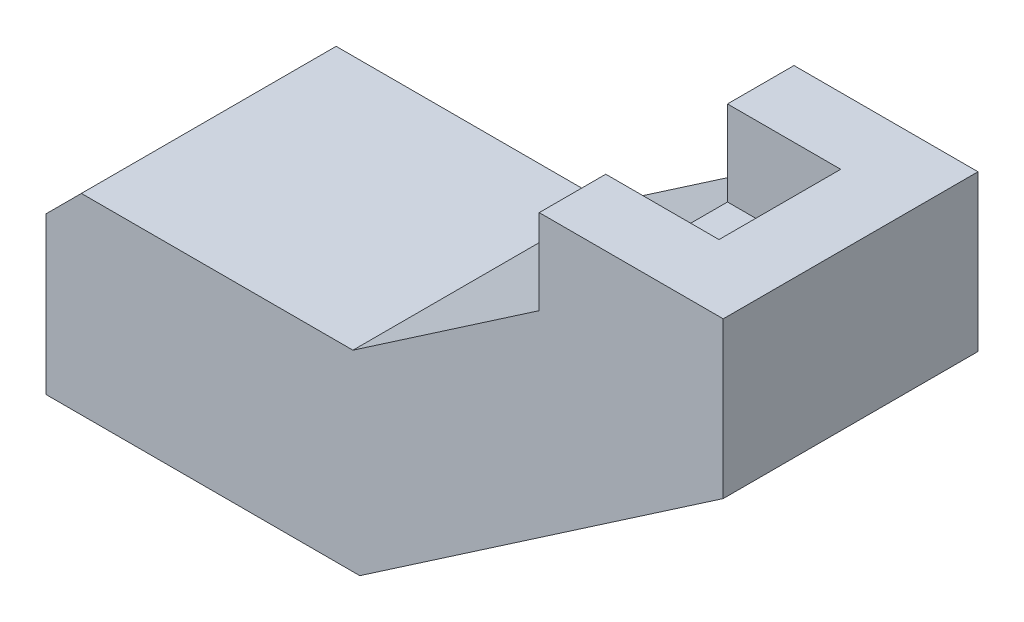
SolidWorks part; units mm, degrees
ref_plane "Front Plane" through (0, 0, 0) normal (0, 0, 1) x (1, 0, 0)
ref_plane "Top Plane" through (0, 0, 0) normal (0, 1, 0) x (1, 0, 0)
ref_plane "Right Plane" through (0, 0, 0) normal (1, 0, 0) x (0, 0, -1)
sketch "Sketch1" plane through (0, 0, 0) normal (0, 0, 1) x (1, 0, 0)
  line L0 (0, 6) -> (5, 6)
  line L1 (5, 6) -> (5, -5)
  line L2 (-20.6795, -22.5563) -> (-49.0563, -22.5563)
  line L4 (-49.0563, -22.5563) -> (-60.5563, -11.0563)
  line L5 (-60.5563, -11.0563) -> (-46.4142, 3.0858)
  line L6 (-46.4142, 3.0858) -> (-34.3284, -9)
  line L7 (-34.3284, -9) -> (-21.1642, -9)
  line L8 (-8, -9) -> (-8, 0) construction
  line L9 (0, 0) -> (-30, 0) construction
  line L10 (-8, 0) -> (0, 0)
  line L11 (0, 0) -> (0, 6)
  line L12 (-39.25, -1.25) -> (-54.8063, -16.8063) construction
  line L13 (-45, 4.5) -> (-46.4142, 3.0858) construction
  line L14 (-33.5, -7) -> (-54.8063, -16.8063) construction
  line L15 (-54.8063, -16.8063) -> (-45, 4.5) construction
  line L16 (-8, 0) -> (-21.1642, -9)
  line L17 (5, -5) -> (-20.6795, -22.5563)
  line L18 (-8, -9) -> (-8, -17) construction
  line L19 (-33.5, -7) -> (-45, 4.5) construction
  line L20 (5, -17) -> (-8, -17) construction
  line L21 (-33.5, -7) -> (-45, 4.5) construction
  line L22 (-8, -17) -> (-20.6795, -22.5563) construction
  line L23 (5, -5) -> (5, -17) construction
  line L24 (-21.1642, -9) -> (-8, -9) construction
  line L25 (0, 0) -> (-30, 0) construction
  dimension "D1" = 2
  dimension "D2" = 8
  dimension "D3" = 2
  dimension "D4" = 20
  dimension "D5" = 8
  dimension "D6" = 5
  dimension "D7" = 11
extrude "Boss-Extrude1" add sketch "Sketch1" against normal blind 13 and the other way blind 5
sketch "Sketch2" plane through (0, 0, 0) normal (0, 1, 0) x (1, 0, 0)
  circle A0 centre (-3, 3.95) radius 1.5
  circle A1 centre (-3, 3.95) radius 1.5 construction
extrude "Cut-Extrude1" cut sketch "Sketch2" against normal through all
sketch "Sketch4" plane through (0, 0, 0) normal (0, 1, 0) x (1, 0, 0)
  line L0 (0, -5) -> (0, 13) construction
  line L1 (-8, -5) -> (0, -5)
  line L2 (-8, -5) -> (-8, -0.3)
  line L3 (-8, -0.3) -> (0, -0.3)
  line L4 (0, -5) -> (0, -0.3)
  line L5 (0, 0) -> (-30, 0) construction
  line L6 (-8, 13) -> (0, 13)
  line L7 (-8, 13) -> (-8, 8.3)
  line L8 (-8, 8.3) -> (0, 8.3)
  line L9 (0, 13) -> (0, 8.3)
  line L10 (-8, -5) -> (-8, 13) construction
  line L11 (0, -5) -> (-8, -5) construction
  dimension "D1" = 0.3
extrude "Boss-Extrude2" add sketch "Sketch4" along normal up to surface (6 mm away) up to face at (2.5, 6, -4)
sketch "Sketch5" plane through (0, 0, 0) normal (0, 1, 0) x (1, 0, 0)
  line L0 (-1.2679, 0.95) -> (-4.7321, 0.95)
  line L1 (-4.7321, 0.95) -> (-6.4641, 3.95)
  line L2 (-6.4641, 3.95) -> (-4.7321, 6.95)
  line L3 (-4.7321, 6.95) -> (-1.2679, 6.95)
  line L4 (-1.2679, 6.95) -> (0.4641, 3.95)
  line L5 (0.4641, 3.95) -> (-1.2679, 0.95)
  circle A0 centre (-3, 3.95) radius 3.4641 construction
  circle A1 centre (-3, 3.95) radius 1.5 construction
  dimension "D1" = 6
extrude "Cut-Extrude3" cut sketch "Sketch5" against normal through all from offset 5 offset against normal yes
sketch "Sketch6" plane through (0, 0, 5) normal (0, 0, 1) x (1, 0, 0)
  line L2 (-60.5563, -11.0563) -> (-49.0563, -22.5563) construction
  line L10 (-54.8063, -16.8063) -> (-30.3048, 7.6952) construction
  line L11 (-33.5, -7) -> (-45, 4.5) construction
  line L12 (-53.1, -15.1) -> (-25.85, -15.1) construction
  line L13 (-45.997, -12) -> (-25.85, -12) construction
  line L14 (-45.997, -12) -> (-45.997, -18.2) construction
  line L15 (-45.997, -18.2) -> (-25.85, -18.2) construction
  line L16 (-25.85, -12) -> (-25.85, -18.2) construction
  line L17 (-53.1, -15.1) -> (-60.85, -15.1) construction
  line L18 (0, 0) -> (-30, 0) construction
  line L19 (-21.1642, -9) -> (-34.3284, -9) construction
  line L20 (-42.85, -22.5563) -> (-49.0563, -22.5563)
  line L21 (-49.0563, -22.5563) -> (-20.6795, -22.5563) construction
  line L22 (-49.0563, -22.5563) -> (-60.5563, -11.0563)
  line L23 (-46.4142, 3.0858) -> (-60.5563, -11.0563) construction
  line L24 (-60.5563, -11.0563) -> (-46.4142, 3.0858)
  line L25 (-46.4142, 3.0858) -> (-45.85, 2.5216)
  line L26 (-34.3284, -9) -> (-46.4142, 3.0858) construction
  line L27 (-42.85, -9) -> (-42.85, -22.5563)
  line L28 (-34.3284, -9) -> (-42.85, -9)
  line L29 (-46.4142, 3.0858) -> (-34.3284, -9)
  circle A0 centre (-53.1, -15.1) radius 7.75 construction
  line M24 (-34.3284, -9) -> (-46.4142, 3.0858)
  line M25 (-46.4142, 3.0858) -> (-60.5563, -11.0563)
  line M26 (-60.5563, -11.0563) -> (-49.0563, -22.5563)
  line M27 (-49.0563, -22.5563) -> (-20.6795, -22.5563)
  dimension "D1" = 15.5
  dimension "D2" = 6.2
  dimension "D3" = 35
  dimension "D4" = 3
  dimension "D5" = 17
extrude "Cut-Extrude4" cut sketch "Sketch6" against normal through all contours L28 L27 M24 M25 M26 M27 region at (-48.1741, -10.2401, 5)
ref_axis "Axis1" through (-3, -5, -3.95) along (0, 1, 0)
ref_plane "Plane1" through (0, 0, -3.95) normal (0, 0, 1) x (1, 0, 0)
sketch "Sketch7" plane through (0, 0, -3.95) normal (0, 0, 1) x (1, 0, 0)
  line L0 (-45.997, -12) -> (-45.997, -18.2) construction
  line L1 (-25.85, -12) -> (-25.85, -18.2) construction
  line L4 (-45.997, -18.2) -> (-25.85, -18.2) construction
  line L5 (-45.997, -12) -> (-45.997, -15.1)
  line L6 (-25.85, -12.35) -> (-25.85, -15.1) construction
  line L7 (-45.997, -12) -> (-39.7903, -12)
  line L8 (-45.997, -15.1) -> (-25.85, -15.1)
  line L9 (-45.997, -18.2) -> (-25.85, -18.2) construction
  line L10 (-39.7903, -12) -> (-25.85, -12) construction
  line L11 (-25.85, -15.1) -> (-25.85, -18.2) construction
  line L12 (-45.997, -15.1) -> (-45.997, -18.2) construction
  line L13 (-53.2914, -15.1) -> (-45.997, -15.1) construction
  line L14 (-38.2903, -12.35) -> (-25.85, -12.35)
  line L15 (-46.2903, -11.4) -> (-43.2903, -11.4)
  line L16 (-43.2903, -11.4) -> (-43.2903, -12)
  line L17 (-43.2903, -12) -> (-39.7903, -12)
  line L18 (-39.7903, -12) -> (-38.2903, -12.35)
  line L19 (-25.85, -12) -> (-25.85, -12.35) construction
  line L20 (-53.1, -15.1) -> (-25.85, -15.1) construction
  line L21 (-25.85, -12.35) -> (-24.85, -12.85)
  line L22 (-24.85, -12.85) -> (-24.85, -15.1)
  line L23 (-24.85, -15.1) -> (-25.85, -15.1)
  circle A2 centre (-53.1, -15.1) radius 7.75 construction
  dimension "D1" = 3.5
  dimension "D2" = 3
  dimension "D3" = 3.7
  dimension "D4" = 3.1
  dimension "D5" = 2.75
  dimension "D6" = 1.5
  dimension "D7" = 1
  dimension "D8" = 0.5
revolve "Cut-Revolve1" cut sketch "Sketch7" angle 360 about L8 region at (-35.7517, -13.6677, -3.95)
chamfer "Chamfer1" distance 2.5 angle 45 1 edges at (-42.85, -9, -4)
